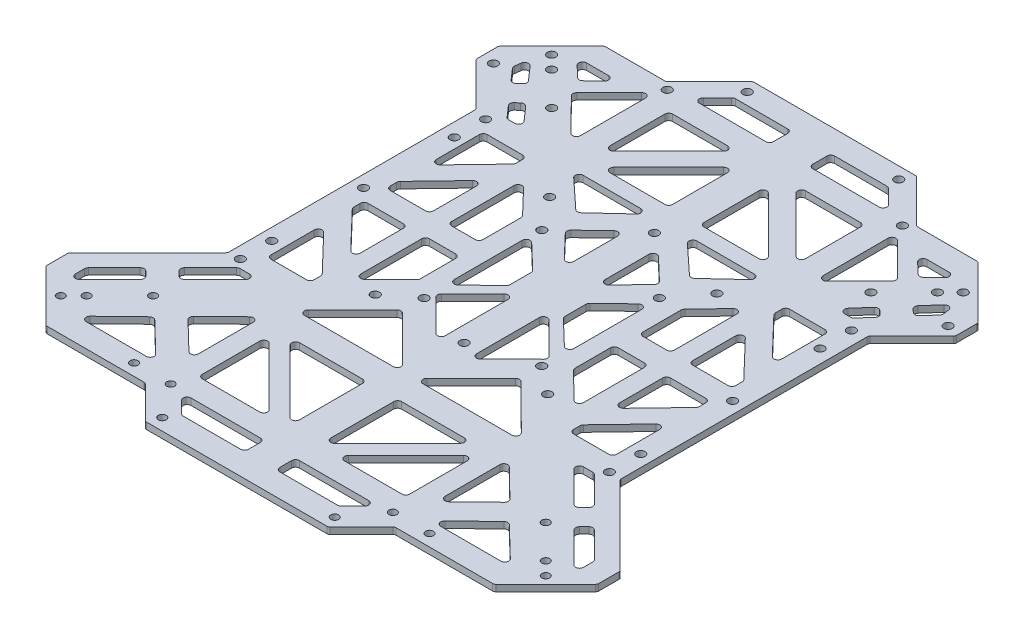
SolidWorks part; units mm, degrees
ref_plane "Ön Düzlem" through (0, 0, 0) normal (0, 0, 1) x (1, 0, 0)
ref_plane "Üst Düzlem" through (0, 0, 0) normal (0, 1, 0) x (1, 0, 0)
ref_plane "Sağ Düzlem" through (0, 0, 0) normal (1, 0, 0) x (0, 0, -1)
sketch "Çizim1" plane through (0, 0, 0) normal (0, 1, 0) x (1, 0, 0)
  line L0 (-126.5115, 0) -> (-22.8808, 0) construction
  line L1 (0, -165.8604) -> (0, 125.495) construction
  line L10 (105.5269, -77.9056) -> (75.1213, -47.5)
  line L11 (105.5269, -86.6056) -> (105.5269, -77.9056)
  line L12 (85.7279, -106.4046) -> (105.5269, -86.6056)
  line L13 (47.7279, -106.4046) -> (85.7279, -106.4046)
  line L14 (35, -119.1325) -> (47.7279, -106.4046)
  line L15 (35, -119.1325) -> (-35, -119.1325)
  line L17 (75.1213, -47.5) -> (75.1213, 0)
  line L19 (6, -104.1325) -> (6, -108.6325)
  line L20 (7.5, -110.1325) -> (29.5, -110.1325)
  line L21 (30.5607, -109.6932) -> (35.0607, -105.1932)
  line L22 (34, -102.6325) -> (7.5, -102.6325)
  line L24 (39.6933, -70.6325) -> (39.6933, -92.6325)
  line L25 (38.1933, -94.1325) -> (16.1933, -94.1325)
  line L26 (15.1326, -91.5718) -> (37.1326, -69.5718)
  line L27 (6, -65.0493) -> (6, -89.1325)
  line L28 (8.5625, -90.1913) -> (32.5625, -66.1081)
  line L29 (31.5, -63.5493) -> (7.5, -63.5493)
  line L30 (66.8113, -83.7022) -> (55.3113, -94.8265)
  line L31 (56.3542, -97.4046) -> (79.3542, -97.4046)
  line L32 (80.3971, -94.8265) -> (68.8971, -83.7022)
  line L36 (49.7362, -87.6977) -> (60.5174, -77.2687)
  line L37 (60.5247, -75.1195) -> (49.7434, -64.5485)
  line L38 (47.1933, -65.6196) -> (47.1933, -86.6196)
  line L39 (21.6344, -34.0457) -> (4.6344, -50.9868)
  line L40 (5.6933, -53.5493) -> (39.6933, -53.5493)
  line L41 (40.7521, -50.9868) -> (23.7521, -34.0457)
  line L42 (6, -9.3078) -> (6, -33.3078)
  line L43 (8.5588, -34.3703) -> (20.6004, -22.3703)
  line L44 (20.6004, -20.2453) -> (8.5588, -8.2453)
  line L45 (10.5, 4) -> (10.5, -4)
  line L46 (10.9615, -5.0824) -> (20.3424, -14.0824)
  line L47 (22.8808, -13) -> (22.8808, 13)
  line L49 (84.7746, -69.1741) -> (83.0069, -70.9419)
  line L50 (83.0069, -73.0632) -> (94.6741, -84.7305)
  line L51 (97.2348, -83.6698) -> (97.2348, -80.1343)
  line L52 (96.7954, -79.0736) -> (86.8959, -69.1741)
  line L53 (87.603, -59.9817) -> (82.3234, -65.2614) construction
  line L54 (63.915, -50.35) -> (67.4505, -50.35)
  line L55 (74.5216, -64.5779) -> (62.8543, -52.9107)
  line L56 (78.4107, -62.8102) -> (76.6429, -64.5779)
  line L57 (68.5112, -50.7893) -> (78.4107, -60.6888)
  line L58 (51.1213, -41.35) -> (64.6213, -41.35)
  line L59 (66.1213, -39.85) -> (66.1213, -23.35)
  line L60 (63.5389, -22.3115) -> (50.0389, -36.3828)
  line L61 (49.6213, -37.4212) -> (49.6213, -39.85)
  line L62 (49.6213, -5.7546) -> (49.6213, -22.2546)
  line L63 (52.2037, -23.293) -> (65.7037, -9.2218)
  line L64 (66.1213, -8.1833) -> (66.1213, -5.7546)
  line L65 (64.6213, -4.2546) -> (51.1213, -4.2546)
  line L66 (29.6213, -5.75) -> (29.6213, -19.25)
  line L67 (30.0715, -20.3214) -> (40.0715, -30.1194)
  line L68 (42.6213, -29.048) -> (42.6213, -5.75)
  line L69 (41.1213, -4.25) -> (31.1213, -4.25)
  line L70 (-105.5269, -86.6056) -> (-105.5269, -77.9056)
  line L71 (-105.5269, -77.9056) -> (-75.1213, -47.5)
  line L72 (-85.7279, -106.4046) -> (-105.5269, -86.6056)
  line L73 (-87.603, -59.9817) -> (-82.3234, -65.2614) construction
  line L74 (-41.1213, -4.25) -> (-31.1213, -4.25)
  line L75 (-42.6213, -29.048) -> (-42.6213, -5.75)
  line L76 (-30.0715, -20.3214) -> (-40.0715, -30.1194)
  line L77 (-29.6213, -5.75) -> (-29.6213, -19.25)
  line L78 (-64.6213, -4.2546) -> (-51.1213, -4.2546)
  line L79 (-66.1213, -8.1833) -> (-66.1213, -5.7546)
  line L80 (-52.2037, -23.293) -> (-65.7037, -9.2218)
  line L81 (-49.6213, -5.7546) -> (-49.6213, -22.2546)
  line L82 (-49.6213, -37.4212) -> (-49.6213, -39.85)
  line L83 (-63.5389, -22.3115) -> (-50.0389, -36.3828)
  line L84 (-66.1213, -39.85) -> (-66.1213, -23.35)
  line L85 (-51.1213, -41.35) -> (-64.6213, -41.35)
  line L86 (-68.5112, -50.7893) -> (-78.4107, -60.6888)
  line L87 (-78.4107, -62.8102) -> (-76.6429, -64.5779)
  line L88 (-74.5216, -64.5779) -> (-62.8543, -52.9107)
  line L89 (-63.915, -50.35) -> (-67.4505, -50.35)
  line L90 (-96.7954, -79.0736) -> (-86.8959, -69.1741)
  line L91 (-97.2348, -83.6698) -> (-97.2348, -80.1343)
  line L92 (-83.0069, -73.0632) -> (-94.6741, -84.7305)
  line L93 (-84.7746, -69.1741) -> (-83.0069, -70.9419)
  line L95 (-22.8808, -13) -> (-22.8808, 0)
  line L96 (-10.9615, -5.0824) -> (-20.3424, -14.0824)
  line L97 (-10.5, 0) -> (-10.5, -4)
  line L98 (-20.6004, -20.2453) -> (-8.5588, -8.2453)
  line L99 (-8.5588, -34.3703) -> (-20.6004, -22.3703)
  line L100 (-6, -9.3078) -> (-6, -33.3078)
  line L101 (-40.7521, -50.9868) -> (-23.7521, -34.0457)
  line L102 (-5.6933, -53.5493) -> (-39.6933, -53.5493)
  line L103 (-21.6344, -34.0457) -> (-4.6344, -50.9868)
  line L104 (-47.1933, -65.6196) -> (-47.1933, -86.6196)
  line L105 (-60.5247, -75.1195) -> (-49.7434, -64.5485)
  line L106 (-49.7362, -87.6977) -> (-60.5174, -77.2687)
  line L107 (-80.3971, -94.8265) -> (-68.8971, -83.7022)
  line L108 (-56.3542, -97.4046) -> (-79.3542, -97.4046)
  line L109 (-66.8113, -83.7022) -> (-55.3113, -94.8265)
  line L110 (-31.5, -63.5493) -> (-7.5, -63.5493)
  line L111 (-8.5625, -90.1913) -> (-32.5625, -66.1081)
  line L112 (-6, -65.0493) -> (-6, -89.1325)
  line L113 (-15.1326, -91.5718) -> (-37.1326, -69.5718)
  line L114 (-38.1933, -94.1325) -> (-16.1933, -94.1325)
  line L115 (-39.6933, -70.6325) -> (-39.6933, -92.6325)
  line L116 (-34, -102.6325) -> (-7.5, -102.6325)
  line L117 (-30.5607, -109.6932) -> (-35.0607, -105.1932)
  line L118 (-7.5, -110.1325) -> (-29.5, -110.1325)
  line L119 (-6, -104.1325) -> (-6, -108.6325)
  line L120 (-75.1213, -47.5) -> (-75.1213, 0)
  line L121 (-35, -119.1325) -> (-47.7279, -106.4046)
  line L122 (-47.7279, -106.4046) -> (-85.7279, -106.4046)
  line L124 (75.1213, 0) -> (75.1213, 47.5)
  line L125 (75.1213, 47.5) -> (91.7383, 64.117)
  line L126 (91.7383, 64.117) -> (91.7383, 72.817)
  line L127 (91.7383, 72.817) -> (71.4444, 93.111)
  line L128 (71.4444, 93.111) -> (47.9444, 93.111)
  line L129 (47.9444, 93.111) -> (31.3274, 109.728)
  line L130 (31.3274, 109.728) -> (-31.3274, 109.728)
  line L131 (63.5389, 22.3115) -> (50.0389, 36.3828)
  line L132 (66.1213, 39.85) -> (66.1213, 23.35)
  line L133 (51.1213, 41.35) -> (64.6213, 41.35)
  line L134 (49.6213, 37.4212) -> (49.6213, 39.85)
  line L135 (66.1213, 8.1833) -> (66.1213, 5.7546)
  line L136 (52.2037, 23.293) -> (65.7037, 9.2218)
  line L137 (49.6213, 5.7546) -> (49.6213, 22.2546)
  line L138 (64.6213, 4.2546) -> (51.1213, 4.2546)
  line L139 (41.1213, 4.2546) -> (32.1213, 4.2546)
  line L140 (30.6213, 5.7546) -> (30.6213, 20.2546)
  line L141 (31.0389, 21.293) -> (40.0389, 30.6739)
  line L142 (42.6213, 29.6354) -> (42.6213, 5.7546)
  line L143 (10.9615, 5.0824) -> (20.3424, 14.0824)
  line L144 (22.8808, 0) -> (141.8188, 0) construction
  line L145 (62.0023, 52.8424) -> (66.6337, 58.0913)
  line L146 (68.7509, 58.2236) -> (70.0256, 57.0989)
  line L147 (70.1579, 54.9817) -> (66.519, 50.8576)
  line L150 (65.3942, 50.35) -> (63.1271, 50.35)
  line L151 (70.1198, 63.017) -> (74.1298, 59.4788) construction
  line L152 (78.0974, 63.9797) -> (81.7363, 68.1038)
  line L153 (74.7055, 64.9722) -> (75.9802, 63.8474)
  line L154 (79.2045, 72.3382) -> (74.5731, 67.0894)
  line L155 (82.0999, 69.283) -> (81.8176, 71.5326)
  line L156 (60.9579, 84.111) -> (69.3579, 84.111)
  line L157 (70.3923, 81.5248) -> (66.1923, 77.5248)
  line L158 (64.1234, 77.5248) -> (59.9234, 81.5248)
  line L159 (6, 32.6354) -> (6, 15.8354)
  line L160 (8.585, 14.7997) -> (16.976, 23.5902)
  line L161 (16.9266, 25.7109) -> (8.5357, 33.7204)
  line L162 (9.7302, 43.598) -> (20.7302, 33.4)
  line L163 (22.7698, 33.4) -> (33.7698, 43.598)
  line L164 (32.75, 46.198) -> (10.75, 46.198)
  line L165 (9, 100.728) -> (29.0094, 100.728)
  line L166 (30.071, 100.2877) -> (35.4616, 94.8877)
  line L167 (34.4, 92.328) -> (9, 92.328)
  line L168 (7.5, 93.828) -> (7.5, 99.228)
  line L169 (6, 74.698) -> (6, 53.698)
  line L170 (7.5, 52.198) -> (28.5, 52.198)
  line L171 (29.5607, 54.7587) -> (8.5607, 75.7587)
  line L172 (16.4335, 73.1892) -> (24.0883, 65.5343) construction
  line L173 (37.4246, 82.1227) -> (37.4246, 61.1227)
  line L174 (14.9246, 83.6227) -> (35.9246, 83.6227)
  line L175 (34.864, 60.062) -> (13.864, 81.062)
  line L176 (46.4246, 83.7244) -> (46.4246, 58.8244)
  line L177 (48.9917, 57.7702) -> (61.3661, 70.2958)
  line L178 (61.3597, 72.4107) -> (48.9853, 84.785)
  line L179 (-10.5, 0) -> (10.5, 0) construction
  line L180 (-22.8808, -13) -> (-22.8808, 13)
  line L181 (-10.5, 4) -> (-10.5, -4)
  line L182 (-75.1213, 0) -> (-75.1213, 47.5)
  line L183 (-16.4335, 73.1892) -> (-24.0883, 65.5343) construction
  line L184 (-61.3597, 72.4107) -> (-48.9853, 84.785)
  line L185 (-48.9917, 57.7702) -> (-61.3661, 70.2958)
  line L186 (-46.4246, 83.7244) -> (-46.4246, 58.8244)
  line L187 (-34.864, 60.062) -> (-13.864, 81.062)
  line L188 (-14.9246, 83.6227) -> (-35.9246, 83.6227)
  line L189 (-37.4246, 82.1227) -> (-37.4246, 61.1227)
  line L190 (-29.5607, 54.7587) -> (-8.5607, 75.7587)
  line L191 (-7.5, 52.198) -> (-28.5, 52.198)
  line L192 (-6, 74.698) -> (-6, 53.698)
  line L193 (-7.5, 93.828) -> (-7.5, 99.228)
  line L194 (-34.4, 92.328) -> (-9, 92.328)
  line L195 (-30.071, 100.2877) -> (-35.4616, 94.8877)
  line L196 (-9, 100.728) -> (-29.0094, 100.728)
  line L197 (-32.75, 46.198) -> (-10.75, 46.198)
  line L198 (-22.7698, 33.4) -> (-33.7698, 43.598)
  line L199 (-9.7302, 43.598) -> (-20.7302, 33.4)
  line L200 (-16.9266, 25.7109) -> (-8.5357, 33.7204)
  line L201 (-8.585, 14.7997) -> (-16.976, 23.5902)
  line L202 (-6, 32.6354) -> (-6, 15.8354)
  line L203 (-64.1234, 77.5248) -> (-59.9234, 81.5248)
  line L204 (-70.3923, 81.5248) -> (-66.1923, 77.5248)
  line L205 (-60.9579, 84.111) -> (-69.3579, 84.111)
  line L206 (-82.0999, 69.283) -> (-81.8176, 71.5326)
  line L207 (-79.2045, 72.3382) -> (-74.5731, 67.0894)
  line L208 (-74.7055, 64.9722) -> (-75.9802, 63.8474)
  line L209 (-78.0974, 63.9797) -> (-81.7363, 68.1038)
  line L210 (-10.9615, 5.0824) -> (-20.3424, 14.0824)
  line L211 (-42.6213, 29.6354) -> (-42.6213, 5.7546)
  line L212 (-31.0389, 21.293) -> (-40.0389, 30.6739)
  line L213 (-30.6213, 5.7546) -> (-30.6213, 20.2546)
  line L214 (-41.1213, 4.2546) -> (-32.1213, 4.2546)
  line L215 (-64.6213, 4.2546) -> (-51.1213, 4.2546)
  line L216 (-49.6213, 5.7546) -> (-49.6213, 22.2546)
  line L217 (-52.2037, 23.293) -> (-65.7037, 9.2218)
  line L218 (-66.1213, 8.1833) -> (-66.1213, 5.7546)
  line L219 (-49.6213, 37.4212) -> (-49.6213, 39.85)
  line L220 (-51.1213, 41.35) -> (-64.6213, 41.35)
  line L221 (-66.1213, 39.85) -> (-66.1213, 23.35)
  line L222 (-63.5389, 22.3115) -> (-50.0389, 36.3828)
  line L223 (-47.9444, 93.111) -> (-31.3274, 109.728)
  line L224 (-71.4444, 93.111) -> (-47.9444, 93.111)
  line L225 (-91.7383, 72.817) -> (-71.4444, 93.111)
  line L226 (-91.7383, 64.117) -> (-91.7383, 72.817)
  line L227 (-75.1213, 47.5) -> (-91.7383, 64.117)
  line L228 (-70.1579, 54.9817) -> (-66.519, 50.8576)
  line L229 (-68.7509, 58.2236) -> (-70.0256, 57.0989)
  line L230 (-62.0023, 52.8424) -> (-66.6337, 58.0913)
  line L231 (-65.3942, 50.35) -> (-63.1271, 50.35)
  arc A0 (29.5, -110.1325) -> (30.5607, -109.6932) centre (29.5, -108.6325) ccw
  arc A1 (35.0607, -105.1932) -> (34, -102.6325) centre (34, -104.1325) ccw
  arc A2 (6, -104.1325) -> (7.5, -102.6325) centre (7.5, -104.1325) cw
  arc A3 (6, -108.6325) -> (7.5, -110.1325) centre (7.5, -108.6325) ccw
  arc A4 (39.6933, -70.6325) -> (37.1326, -69.5718) centre (38.1933, -70.6325) ccw
  arc A5 (39.6933, -92.6325) -> (38.1933, -94.1325) centre (38.1933, -92.6325) cw
  arc A6 (16.1933, -94.1325) -> (15.1326, -91.5718) centre (16.1933, -92.6325) cw
  arc A7 (6, -89.1325) -> (8.5625, -90.1913) centre (7.5, -89.1325) ccw
  arc A8 (32.5625, -66.1081) -> (31.5, -63.5493) centre (31.5, -65.0493) ccw
  arc A9 (6, -65.0493) -> (7.5, -63.5493) centre (7.5, -65.0493) cw
  arc A10 (79.3542, -97.4046) -> (80.3971, -94.8265) centre (79.3542, -95.9046) ccw
  arc A11 (55.3113, -94.8265) -> (56.3542, -97.4046) centre (56.3542, -95.9046) ccw
  arc A12 (66.8113, -83.7022) -> (68.8971, -83.7022) centre (67.8542, -84.7803) cw
  arc A16 (60.5174, -77.2687) -> (60.5247, -75.1195) centre (59.4745, -76.1905) ccw
  arc A17 (49.7434, -64.5485) -> (47.1933, -65.6196) centre (48.6933, -65.6196) ccw
  arc A18 (49.7362, -87.6977) -> (47.1933, -86.6196) centre (48.6933, -86.6196) cw
  arc A19 (39.6933, -53.5493) -> (40.7521, -50.9868) centre (39.6933, -52.0493) ccw
  arc A20 (4.6344, -50.9868) -> (5.6933, -53.5493) centre (5.6933, -52.0493) ccw
  arc A21 (21.6344, -34.0457) -> (23.7521, -34.0457) centre (22.6933, -35.1082) cw
  arc A22 (6, -9.3078) -> (8.5588, -8.2453) centre (7.5, -9.3078) cw
  arc A23 (20.6004, -22.3703) -> (20.6004, -20.2453) centre (19.5416, -21.3078) ccw
  arc A24 (6, -33.3078) -> (8.5588, -34.3703) centre (7.5, -33.3078) ccw
  arc A25 (20.3424, -14.0824) -> (22.8808, -13) centre (21.3808, -13) ccw
  arc A26 (10.5, -4) -> (10.9615, -5.0824) centre (12, -4) ccw
  arc A27 (83.0069, -70.9419) -> (83.0069, -73.0632) centre (84.0675, -72.0025) ccw
  arc A28 (84.7746, -69.1741) -> (86.8959, -69.1741) centre (85.8353, -70.2348) cw
  arc A29 (97.2348, -80.1343) -> (96.7954, -79.0736) centre (95.7348, -80.1343) ccw
  arc A30 (94.6741, -84.7305) -> (97.2348, -83.6698) centre (95.7348, -83.6698) ccw
  arc A31 (62.8543, -52.9107) -> (63.915, -50.35) centre (63.915, -51.85) cw
  arc A32 (76.6429, -64.5779) -> (74.5216, -64.5779) centre (75.5822, -63.5173) cw
  arc A33 (78.4107, -62.8102) -> (78.4107, -60.6888) centre (77.35, -61.7495) ccw
  arc A34 (67.4505, -50.35) -> (68.5112, -50.7893) centre (67.4505, -51.85) cw
  arc A35 (66.1213, -23.35) -> (63.5389, -22.3115) centre (64.6213, -23.35) ccw
  arc A36 (64.6213, -41.35) -> (66.1213, -39.85) centre (64.6213, -39.85) ccw
  arc A37 (51.1213, -41.35) -> (49.6213, -39.85) centre (51.1213, -39.85) cw
  arc A38 (50.0389, -36.3828) -> (49.6213, -37.4212) centre (51.1213, -37.4212) ccw
  arc A39 (66.1213, -5.7546) -> (64.6213, -4.2546) centre (64.6213, -5.7546) ccw
  arc A40 (65.7037, -9.2218) -> (66.1213, -8.1833) centre (64.6213, -8.1833) ccw
  arc A41 (49.6213, -22.2546) -> (52.2037, -23.293) centre (51.1213, -22.2546) ccw
  arc A42 (49.6213, -5.7546) -> (51.1213, -4.2546) centre (51.1213, -5.7546) cw
  arc A43 (29.6213, -5.75) -> (31.1213, -4.25) centre (31.1213, -5.75) cw
  arc A44 (42.6213, -5.75) -> (41.1213, -4.25) centre (41.1213, -5.75) ccw
  arc A45 (40.0715, -30.1194) -> (42.6213, -29.048) centre (41.1213, -29.048) ccw
  arc A46 (29.6213, -19.25) -> (30.0715, -20.3214) centre (31.1213, -19.25) ccw
  arc A47 (-29.6213, -19.25) -> (-30.0715, -20.3214) centre (-31.1213, -19.25) cw
  arc A48 (-40.0715, -30.1194) -> (-42.6213, -29.048) centre (-41.1213, -29.048) cw
  arc A49 (-42.6213, -5.75) -> (-41.1213, -4.25) centre (-41.1213, -5.75) cw
  arc A50 (-29.6213, -5.75) -> (-31.1213, -4.25) centre (-31.1213, -5.75) ccw
  arc A51 (-49.6213, -5.7546) -> (-51.1213, -4.2546) centre (-51.1213, -5.7546) ccw
  arc A52 (-49.6213, -22.2546) -> (-52.2037, -23.293) centre (-51.1213, -22.2546) cw
  arc A53 (-65.7037, -9.2218) -> (-66.1213, -8.1833) centre (-64.6213, -8.1833) cw
  arc A54 (-66.1213, -5.7546) -> (-64.6213, -4.2546) centre (-64.6213, -5.7546) cw
  arc A55 (-50.0389, -36.3828) -> (-49.6213, -37.4212) centre (-51.1213, -37.4212) cw
  arc A56 (-51.1213, -41.35) -> (-49.6213, -39.85) centre (-51.1213, -39.85) ccw
  arc A57 (-64.6213, -41.35) -> (-66.1213, -39.85) centre (-64.6213, -39.85) cw
  arc A58 (-66.1213, -23.35) -> (-63.5389, -22.3115) centre (-64.6213, -23.35) cw
  arc A59 (-67.4505, -50.35) -> (-68.5112, -50.7893) centre (-67.4505, -51.85) ccw
  arc A60 (-78.4107, -62.8102) -> (-78.4107, -60.6888) centre (-77.35, -61.7495) cw
  arc A61 (-76.6429, -64.5779) -> (-74.5216, -64.5779) centre (-75.5822, -63.5173) ccw
  arc A62 (-62.8543, -52.9107) -> (-63.915, -50.35) centre (-63.915, -51.85) ccw
  arc A63 (-94.6741, -84.7305) -> (-97.2348, -83.6698) centre (-95.7348, -83.6698) cw
  arc A64 (-97.2348, -80.1343) -> (-96.7954, -79.0736) centre (-95.7348, -80.1343) cw
  arc A65 (-84.7746, -69.1741) -> (-86.8959, -69.1741) centre (-85.8353, -70.2348) ccw
  arc A66 (-83.0069, -70.9419) -> (-83.0069, -73.0632) centre (-84.0675, -72.0025) cw
  arc A67 (-10.5, -4) -> (-10.9615, -5.0824) centre (-12, -4) cw
  arc A68 (-20.3424, -14.0824) -> (-22.8808, -13) centre (-21.3808, -13) cw
  arc A69 (-6, -33.3078) -> (-8.5588, -34.3703) centre (-7.5, -33.3078) cw
  arc A70 (-20.6004, -22.3703) -> (-20.6004, -20.2453) centre (-19.5416, -21.3078) cw
  arc A71 (-6, -9.3078) -> (-8.5588, -8.2453) centre (-7.5, -9.3078) ccw
  arc A72 (-21.6344, -34.0457) -> (-23.7521, -34.0457) centre (-22.6933, -35.1082) ccw
  arc A73 (-4.6344, -50.9868) -> (-5.6933, -53.5493) centre (-5.6933, -52.0493) cw
  arc A74 (-39.6933, -53.5493) -> (-40.7521, -50.9868) centre (-39.6933, -52.0493) cw
  arc A75 (-49.7362, -87.6977) -> (-47.1933, -86.6196) centre (-48.6933, -86.6196) ccw
  arc A76 (-49.7434, -64.5485) -> (-47.1933, -65.6196) centre (-48.6933, -65.6196) cw
  arc A77 (-60.5174, -77.2687) -> (-60.5247, -75.1195) centre (-59.4745, -76.1905) cw
  arc A78 (-66.8113, -83.7022) -> (-68.8971, -83.7022) centre (-67.8542, -84.7803) ccw
  arc A79 (-55.3113, -94.8265) -> (-56.3542, -97.4046) centre (-56.3542, -95.9046) cw
  arc A80 (-79.3542, -97.4046) -> (-80.3971, -94.8265) centre (-79.3542, -95.9046) cw
  arc A81 (-6, -65.0493) -> (-7.5, -63.5493) centre (-7.5, -65.0493) ccw
  arc A82 (-32.5625, -66.1081) -> (-31.5, -63.5493) centre (-31.5, -65.0493) cw
  arc A83 (-6, -89.1325) -> (-8.5625, -90.1913) centre (-7.5, -89.1325) cw
  arc A84 (-16.1933, -94.1325) -> (-15.1326, -91.5718) centre (-16.1933, -92.6325) ccw
  arc A85 (-39.6933, -92.6325) -> (-38.1933, -94.1325) centre (-38.1933, -92.6325) ccw
  arc A86 (-39.6933, -70.6325) -> (-37.1326, -69.5718) centre (-38.1933, -70.6325) cw
  arc A87 (-6, -108.6325) -> (-7.5, -110.1325) centre (-7.5, -108.6325) cw
  arc A88 (-6, -104.1325) -> (-7.5, -102.6325) centre (-7.5, -104.1325) ccw
  arc A89 (-35.0607, -105.1932) -> (-34, -102.6325) centre (-34, -104.1325) cw
  arc A90 (-29.5, -110.1325) -> (-30.5607, -109.6932) centre (-29.5, -108.6325) cw
  arc A91 (66.1213, 23.35) -> (63.5389, 22.3115) centre (64.6213, 23.35) cw
  arc A92 (64.6213, 41.35) -> (66.1213, 39.85) centre (64.6213, 39.85) cw
  arc A93 (51.1213, 41.35) -> (49.6213, 39.85) centre (51.1213, 39.85) ccw
  arc A94 (50.0389, 36.3828) -> (49.6213, 37.4212) centre (51.1213, 37.4212) cw
  arc A95 (65.7037, 9.2218) -> (66.1213, 8.1833) centre (64.6213, 8.1833) cw
  arc A96 (49.6213, 22.2546) -> (52.2037, 23.293) centre (51.1213, 22.2546) cw
  arc A97 (66.1213, 5.7546) -> (64.6213, 4.2546) centre (64.6213, 5.7546) cw
  arc A98 (49.6213, 5.7546) -> (51.1213, 4.2546) centre (51.1213, 5.7546) ccw
  arc A99 (32.1213, 4.2546) -> (30.6213, 5.7546) centre (32.1213, 5.7546) cw
  arc A100 (41.1213, 4.2546) -> (42.6213, 5.7546) centre (41.1213, 5.7546) ccw
  arc A101 (40.0389, 30.6739) -> (42.6213, 29.6354) centre (41.1213, 29.6354) cw
  arc A102 (30.6213, 20.2546) -> (31.0389, 21.293) centre (32.1213, 20.2546) cw
  arc A103 (10.5, 4) -> (10.9615, 5.0824) centre (12, 4) cw
  arc A104 (20.3424, 14.0824) -> (22.8808, 13) centre (21.3808, 13) cw
  arc A105 (66.6337, 58.0913) -> (68.7509, 58.2236) centre (67.7584, 57.0989) cw
  arc A106 (70.0256, 57.0989) -> (70.1579, 54.9817) centre (69.0332, 55.9741) cw
  arc A107 (66.519, 50.8576) -> (65.3942, 50.35) centre (65.3942, 51.85) cw
  arc A108 (62.0023, 52.8424) -> (63.1271, 50.35) centre (63.1271, 51.85) ccw
  arc A109 (75.9802, 63.8474) -> (78.0974, 63.9797) centre (76.9726, 64.9722) ccw
  arc A110 (74.5731, 67.0894) -> (74.7055, 64.9722) centre (75.6979, 66.0969) ccw
  arc A111 (81.7363, 68.1038) -> (82.0999, 69.283) centre (80.6115, 69.0963) ccw
  arc A112 (79.2045, 72.3382) -> (81.8176, 71.5326) centre (80.3292, 71.3458) cw
  arc A113 (69.3579, 84.111) -> (70.3923, 81.5248) centre (69.3579, 82.611) cw
  arc A114 (66.1923, 77.5248) -> (64.1234, 77.5248) centre (65.1579, 78.611) cw
  arc A115 (60.9579, 84.111) -> (59.9234, 81.5248) centre (60.9579, 82.611) ccw
  arc A116 (16.976, 23.5902) -> (16.9266, 25.7109) centre (15.8909, 24.6259) ccw
  arc A117 (6, 15.8354) -> (8.585, 14.7997) centre (7.5, 15.8354) ccw
  arc A118 (6, 32.6354) -> (8.5357, 33.7204) centre (7.5, 32.6354) cw
  arc A119 (33.7698, 43.598) -> (32.75, 46.198) centre (32.75, 44.698) ccw
  arc A120 (20.7302, 33.4) -> (22.7698, 33.4) centre (21.75, 34.5) ccw
  arc A121 (9.7302, 43.598) -> (10.75, 46.198) centre (10.75, 44.698) cw
  arc A122 (35.4616, 94.8877) -> (34.4, 92.328) centre (34.4, 93.828) cw
  arc A123 (29.0094, 100.728) -> (30.071, 100.2877) centre (29.0094, 99.228) cw
  arc A124 (9, 100.728) -> (7.5, 99.228) centre (9, 99.228) ccw
  arc A125 (9, 92.328) -> (7.5, 93.828) centre (9, 93.828) cw
  arc A126 (28.5, 52.198) -> (29.5607, 54.7587) centre (28.5, 53.698) ccw
  arc A127 (6, 53.698) -> (7.5, 52.198) centre (7.5, 53.698) ccw
  arc A128 (6, 74.698) -> (8.5607, 75.7587) centre (7.5, 74.698) cw
  arc A129 (35.9246, 83.6227) -> (37.4246, 82.1227) centre (35.9246, 82.1227) cw
  arc A130 (37.4246, 61.1227) -> (34.864, 60.062) centre (35.9246, 61.1227) cw
  arc A131 (14.9246, 83.6227) -> (13.864, 81.062) centre (14.9246, 82.1227) ccw
  arc A132 (46.4246, 83.7244) -> (48.9853, 84.785) centre (47.9246, 83.7244) cw
  arc A133 (46.4246, 58.8244) -> (48.9917, 57.7702) centre (47.9246, 58.8244) ccw
  arc A134 (61.3661, 70.2958) -> (61.3597, 72.4107) centre (60.299, 71.35) ccw
  arc A135 (-61.3661, 70.2958) -> (-61.3597, 72.4107) centre (-60.299, 71.35) cw
  arc A136 (-46.4246, 58.8244) -> (-48.9917, 57.7702) centre (-47.9246, 58.8244) cw
  arc A137 (-46.4246, 83.7244) -> (-48.9853, 84.785) centre (-47.9246, 83.7244) ccw
  arc A138 (-14.9246, 83.6227) -> (-13.864, 81.062) centre (-14.9246, 82.1227) cw
  arc A139 (-37.4246, 61.1227) -> (-34.864, 60.062) centre (-35.9246, 61.1227) ccw
  arc A140 (-35.9246, 83.6227) -> (-37.4246, 82.1227) centre (-35.9246, 82.1227) ccw
  arc A141 (-6, 74.698) -> (-8.5607, 75.7587) centre (-7.5, 74.698) ccw
  arc A142 (-6, 53.698) -> (-7.5, 52.198) centre (-7.5, 53.698) cw
  arc A143 (-28.5, 52.198) -> (-29.5607, 54.7587) centre (-28.5, 53.698) cw
  arc A144 (-9, 92.328) -> (-7.5, 93.828) centre (-9, 93.828) ccw
  arc A145 (-9, 100.728) -> (-7.5, 99.228) centre (-9, 99.228) cw
  arc A146 (-29.0094, 100.728) -> (-30.071, 100.2877) centre (-29.0094, 99.228) ccw
  arc A147 (-35.4616, 94.8877) -> (-34.4, 92.328) centre (-34.4, 93.828) ccw
  arc A148 (-9.7302, 43.598) -> (-10.75, 46.198) centre (-10.75, 44.698) ccw
  arc A149 (-20.7302, 33.4) -> (-22.7698, 33.4) centre (-21.75, 34.5) cw
  arc A150 (-33.7698, 43.598) -> (-32.75, 46.198) centre (-32.75, 44.698) cw
  arc A151 (-6, 32.6354) -> (-8.5357, 33.7204) centre (-7.5, 32.6354) ccw
  arc A152 (-6, 15.8354) -> (-8.585, 14.7997) centre (-7.5, 15.8354) cw
  arc A153 (-16.976, 23.5902) -> (-16.9266, 25.7109) centre (-15.8909, 24.6259) cw
  arc A154 (-60.9579, 84.111) -> (-59.9234, 81.5248) centre (-60.9579, 82.611) cw
  arc A155 (-66.1923, 77.5248) -> (-64.1234, 77.5248) centre (-65.1579, 78.611) ccw
  arc A156 (-69.3579, 84.111) -> (-70.3923, 81.5248) centre (-69.3579, 82.611) ccw
  arc A157 (-79.2045, 72.3382) -> (-81.8176, 71.5326) centre (-80.3292, 71.3458) ccw
  arc A158 (-81.7363, 68.1038) -> (-82.0999, 69.283) centre (-80.6115, 69.0963) cw
  arc A159 (-74.5731, 67.0894) -> (-74.7055, 64.9722) centre (-75.6979, 66.0969) cw
  arc A160 (-75.9802, 63.8474) -> (-78.0974, 63.9797) centre (-76.9726, 64.9722) cw
  arc A161 (-20.3424, 14.0824) -> (-22.8808, 13) centre (-21.3808, 13) ccw
  arc A162 (-10.5, 4) -> (-10.9615, 5.0824) centre (-12, 4) ccw
  arc A163 (-30.6213, 20.2546) -> (-31.0389, 21.293) centre (-32.1213, 20.2546) ccw
  arc A164 (-40.0389, 30.6739) -> (-42.6213, 29.6354) centre (-41.1213, 29.6354) ccw
  arc A165 (-41.1213, 4.2546) -> (-42.6213, 5.7546) centre (-41.1213, 5.7546) cw
  arc A166 (-32.1213, 4.2546) -> (-30.6213, 5.7546) centre (-32.1213, 5.7546) ccw
  arc A167 (-49.6213, 5.7546) -> (-51.1213, 4.2546) centre (-51.1213, 5.7546) cw
  arc A168 (-66.1213, 5.7546) -> (-64.6213, 4.2546) centre (-64.6213, 5.7546) ccw
  arc A169 (-49.6213, 22.2546) -> (-52.2037, 23.293) centre (-51.1213, 22.2546) ccw
  arc A170 (-65.7037, 9.2218) -> (-66.1213, 8.1833) centre (-64.6213, 8.1833) ccw
  arc A171 (-50.0389, 36.3828) -> (-49.6213, 37.4212) centre (-51.1213, 37.4212) ccw
  arc A172 (-51.1213, 41.35) -> (-49.6213, 39.85) centre (-51.1213, 39.85) cw
  arc A173 (-64.6213, 41.35) -> (-66.1213, 39.85) centre (-64.6213, 39.85) ccw
  arc A174 (-66.1213, 23.35) -> (-63.5389, 22.3115) centre (-64.6213, 23.35) ccw
  arc A175 (-70.0256, 57.0989) -> (-70.1579, 54.9817) centre (-69.0332, 55.9741) ccw
  arc A176 (-66.6337, 58.0913) -> (-68.7509, 58.2236) centre (-67.7584, 57.0989) ccw
  arc A177 (-66.519, 50.8576) -> (-65.3942, 50.35) centre (-65.3942, 51.85) ccw
  arc A178 (-62.0023, 52.8424) -> (-63.1271, 50.35) centre (-63.1271, 51.85) cw
  point P14 (75.1213, 0)
  point P24 (0, -119.1325)
  point P29 (-95, 0)
  point P33 (0, 119.1325)
  point P105 (83.8907, -70.058)
  point P152 (42.6213, -32.6177)
  point P155 (29.6213, -19.8803)
  point P298 (0, -119.1325)
  point P299 (-29.6213, -19.8803)
  point P300 (-42.6213, -32.6177)
  point P301 (-75.1213, 0)
  point P357 (67.6261, 59.2161)
  point P360 (71.1503, 56.1064)
  point P363 (66.0711, 50.35)
  point P366 (59.8031, 50.35)
  point P367 (69.3882, 57.6612)
  point P368 (64.2607, 50.35)
  point P577 (0, 109.728)
  dimension "D18" = 1.5
  dimension "D15" = 28
  dimension "D19" = 1.5
  dimension "D24" = 1.5
  dimension "D29" = 1.5
  dimension "D35" = 1.5
  dimension "D39" = 1.5
  dimension "D28" = 1.5
  dimension "D51" = 1.5
  dimension "D55" = 1.5
  dimension "D62" = 1.5
  dimension "D68" = 1.5
  dimension "D75" = 1.5
  dimension "D89" = 1.5
  dimension "D97" = 1.5
  dimension "D102" = 1.5
  dimension "D106" = 1.5
  dimension "D111" = 1.5
  dimension "D112" = 15
  dimension "D113" = 15
  dimension "D115" = 10.75
  dimension "D117" = 1.5
  dimension "D118" = 1.5
  dimension "D119" = 1.5
  dimension "D120" = 1.5
  dimension "D126" = 1.5
  dimension "D127" = 1.5
  dimension "D128" = 1.5
  dimension "D134" = 1.5
  dimension "D135" = 1.5
  dimension "D136" = 1.5
  dimension "D1" = 47.5
  dimension "D2" = 18
  dimension "D3" = 43
  dimension "D4" = 8.7
  dimension "D5" = 28
  dimension "D6" = 38
  dimension "D7" = 35
  dimension "D8" = 135
  dimension "D9" = 225
  dimension "D10" = 135
  dimension "D11" = 135
  dimension "D12" = 135
  dimension "D13" = 7.5
  dimension "D14" = 9
  dimension "D16" = 6
  dimension "D17" = 135
  dimension "D20" = 22
  dimension "D21" = 7.5
  dimension "D22" = 25
  dimension "D23" = 22
  dimension "D25" = 24
  dimension "D26" = 15
  dimension "D27" = 34
  dimension "D30" = 16
  dimension "D31" = 16
  dimension "D32" = 23
  dimension "D33" = 9
  dimension "D34" = 30
  dimension "D36" = 21
  dimension "D37" = 15
  dimension "D38" = 9
  dimension "D40" = 30
  dimension "D41" = 10
  dimension "D42" = 24
  dimension "D43" = 24
  dimension "D44" = 34
  dimension "D45" = 6
  dimension "D46" = 24
  dimension "D47" = 17
  dimension "D48" = 17
  dimension "D49" = 9
  dimension "D50" = 13
  dimension "D52" = 13
  dimension "D53" = 10.5
  dimension "D54" = 4
  dimension "D56" = 7
  dimension "D57" = 5.5
  dimension "D58" = 16.5
  dimension "D59" = 14
  dimension "D60" = 9
  dimension "D61" = 4.5
  dimension "D63" = 13.5
  dimension "D64" = 19.5
  dimension "D65" = 16.5
  dimension "D66" = 9
  dimension "D67" = 9
  dimension "D69" = 19.5
  dimension "D70" = 16.5
  dimension "D71" = 13.5
  dimension "D72" = 9
  dimension "D73" = 7.5
  dimension "D74" = 14
  dimension "D76" = 13.5
  dimension "D77" = 10
  dimension "D78" = 7
  dimension "D79" = 4.25
  dimension "D80" = 47.5
  dimension "D81" = 23.5
  dimension "D82" = 8.7
  dimension "D83" = 28.7
  dimension "D84" = 23.5
  dimension "D85" = 23.5
  dimension "D86" = 135
  dimension "D87" = 135
  dimension "D88" = 7
  dimension "D90" = 12
  dimension "D91" = 13
  dimension "D92" = 14.5
  dimension "D93" = 135
  dimension "D94" = 135
  dimension "D95" = 7
  dimension "D96" = 5.5
  dimension "D98" = 4.7
  dimension "D99" = 9
  dimension "D100" = 8.8
  dimension "D101" = 4.5
  dimension "D103" = 5.8
  dimension "D104" = 9
  dimension "D105" = 8.9
  dimension "D107" = 11.6
  dimension "D108" = 16.8
  dimension "D109" = 6
  dimension "D110" = 9
  dimension "D114" = 22
  dimension "D116" = 21.5
  dimension "D121" = 9
  dimension "D122" = 7.5
  dimension "D123" = 25.4
  dimension "D124" = 7.6301
  dimension "D125" = 8.4
  dimension "D129" = 6
  dimension "D130" = 21
  dimension "D131" = 21
  dimension "D132" = 6
  dimension "D133" = 3.75
  dimension "D137" = 24.9
  dimension "D138" = 5.5
  dimension "D139" = 9
  dimension "D140" = 30
  dimension "D141" = 17.5
extrude "Yükseklik-Ekstrüzyon2" add sketch "Çizim1" along normal blind 2.5 contours L227 L182 L120 L71 L70 L72 L122 L121 L15 L14 L13 L12 L11 L10 L17 L124 L125 L126 L127 L128 L129 L130 L223 L224 L225 L226 A174 L221 A173 L220 A172 L219 A171 L222 A170 L217 A169 L216 A167 L215 A168 L218 A166 L214 A165 L211 A164 L212 region at (0, 0, 8.6044)
sketch "Çizim2" plane through (0, 2.5, 0) normal (0, 1, 0) x (1, 0, 0)
  line L0 (0, 120.2897) -> (0, -148.7666) construction
  line L1 (31.3274, 109.728) -> (-31.3274, 109.728) construction
  line L2 (-177.1004, 0) -> (155.3034, 0) construction
  line L3 (-71.4444, 93.111) -> (-47.9444, 93.111) construction
  line L4 (-75.1213, -47.5) -> (-75.1213, 47.5) construction
  line L5 (35, -119.1325) -> (-35, -119.1325) construction
  line L6 (-47.7279, -106.4046) -> (-85.7279, -106.4046) construction
  line L7 (-105.5269, -86.6056) -> (-105.5269, -77.9056) construction
  line L8 (-73.8202, 75.1929) -> (-89.3625, 90.7351) construction
  line L9 (-75.1213, 47.5) -> (-91.7383, 64.117) construction
  line L10 (-91.7383, 72.817) -> (-71.4444, 93.111) construction
  line L11 (-73.8202, 75.1929) -> (-61.0923, 62.465) construction
  line L12 (-97.9291, -98.8067) -> (-65.4602, -66.3379) construction
  line L13 (-85.7279, -106.4046) -> (-105.5269, -86.6056) construction
  circle A0 centre (-29, 105.228) radius 1.65
  circle A1 centre (-45, 90.611) radius 1.65
  circle A2 centre (0, 40.728) radius 1.65
  circle A3 centre (-73.8202, 75.1929) radius 1.65
  circle A4 centre (-61.0923, 62.465) radius 1.65
  circle A5 centre (-87, 66.111) radius 1.65
  circle A6 centre (-70, 46.111) radius 1.65
  circle A7 centre (-70, 34.111) radius 1.65
  circle A8 centre (-22.5, 20.111) radius 1.65
  circle A9 centre (-70.6213, 0) radius 1.65
  circle A10 centre (22.5, 20.111) radius 1.65
  circle A11 centre (70, 34.111) radius 1.65
  circle A12 centre (70, 46.111) radius 1.65
  circle A13 centre (87, 66.111) radius 1.65
  circle A14 centre (61.0923, 62.465) radius 1.65
  circle A15 centre (73.8202, 75.1929) radius 1.65
  circle A16 centre (45, 90.611) radius 1.65
  circle A17 centre (29, 105.228) radius 1.65
  circle A18 centre (70.6213, 0) radius 1.65
  circle A19 centre (-32, 32.611) radius 1.65
  circle A20 centre (32, 32.611) radius 1.65
  circle A21 centre (-33, -114.6325) radius 1.5
  circle A22 centre (-22.5, -24.9325) radius 1.65
  circle A23 centre (-70.6213, -35.1325) radius 1.65
  circle A24 centre (0, -32.1325) radius 1.65
  circle A27 centre (-87.8563, -88.734) radius 1.5
  circle A28 centre (-56.5269, -101.9046) radius 1.5
  circle A29 centre (-42.5269, -101.9046) radius 1.5
  circle A30 centre (-70.6213, -47.1325) radius 1.65
  circle A31 centre (70.6213, -47.1325) radius 1.65
  circle A32 centre (42.5269, -101.9046) radius 1.5
  circle A33 centre (56.5269, -101.9046) radius 1.5
  circle A34 centre (87.8563, -88.734) radius 1.5
  circle A36 centre (70.6213, -35.1325) radius 1.65
  circle A37 centre (22.5, -24.9325) radius 1.65
  circle A38 centre (33, -114.6325) radius 1.5
  circle A39 centre (-33, -33.1325) radius 1.65
  circle A40 centre (33, -33.1325) radius 1.65
  circle A41 centre (-92.799, -93.6767) radius 1.5
  circle A42 centre (92.799, -93.6767) radius 1.5
  circle A43 centre (-78.7629, 80.1356) radius 1.65
  circle A44 centre (78.7629, 80.1356) radius 1.65
  point P5 (-29, 105.228)
  point P10 (-45, 90.611)
  point P11 (-73.8202, 75.1929)
  point P12 (-61.0923, 62.465)
  point P13 (-87, 66.111)
  point P14 (-70, 46.111)
  point P15 (-32, 32.611)
  point P16 (-70.6213, 0)
  point P17 (-22.5, 20.111)
  point P18 (0, 40.728)
  point P23 (-70, 34.111)
  point P64 (-22.5, -24.9325)
  point P65 (-33, -33.1325)
  point P66 (-70.6213, -35.1325)
  point P67 (-70.6213, -47.1325)
  point P68 (0, -32.1325)
  point P69 (0, -60.1325)
  point P70 (-87.8563, -88.734)
  point P71 (-74.4213, -75.299)
  point P72 (-56.5269, -101.9046)
  point P73 (-42.5269, -101.9046)
  point P74 (-33, -114.6325)
  point P122 (-81.5913, 82.964)
  point P128 (-95.6274, -96.5051)
  dimension "D3" = 3.3
  dimension "D5" = 45
  dimension "D27" = 3
  dimension "D35" = 4
  dimension "D36" = 4
  dimension "D1" = 29
  dimension "D2" = 4.5
  dimension "D4" = 2.5
  dimension "D6" = 10.99
  dimension "D7" = 18
  dimension "D8" = 87
  dimension "D9" = 27
  dimension "D10" = 19
  dimension "D11" = 10.99
  dimension "D12" = 69
  dimension "D13" = 70
  dimension "D14" = 47
  dimension "D15" = 59
  dimension "D16" = 32
  dimension "D17" = 60.5
  dimension "D18" = 22.5
  dimension "D19" = 73
  dimension "D20" = 4.5
  dimension "D21" = 33
  dimension "D22" = 4.5
  dimension "D23" = 4.5
  dimension "D24" = 14
  dimension "D25" = 63
  dimension "D26" = 59
  dimension "D28" = 22.5
  dimension "D29" = 94.2
  dimension "D30" = 86
  dimension "D31" = 33
  dimension "D32" = 12
  dimension "D33" = 4.5
  dimension "D34" = 72
extrude "Kes-Ekstrüzyon1" cut sketch "Çizim2" along direction (0, 1, 0) on the side against the normal through all contours A41 | A42 | A9 | A8 | A10 | A7 | A6 | A4 | A5 | A1 | A3 | A0 | A17 | A16 | A2 | A11 | A12 | A14 | A13 | A15 | A18 | A20 | A19 | A32 | A33 | A34 | A31 | A36 | A37 | A24 | A22 | A23 | A30 | A38 | A21 | A29 | A28 | A27 | A39 | A40 | A43 | A44 region at (-92.799, 2.5, 93.6767) region at (92.799, 2.5, 93.6767)
fillet "Radyus1" radius 1.17 24 edges at (-91.7383, 1.25, -64.117) (-91.7383, 1.25, -72.817) (-71.4444, 1.25, -93.111) (-47.9444, 1.25, -93.111) (-31.3274, 1.25, -109.728) (31.3274, 1.25, -109.728) (47.9444, 1.25, -93.111) (71.4444, 1.25, -93.111) (91.7383, 1.25, -72.817) (91.7383, 1.25, -64.117) (75.1213, 1.25, -47.5) (75.1213, 1.25, 47.5) (105.5269, 1.25, 77.9056) (105.5269, 1.25, 86.6056) (85.7279, 1.25, 106.4046) (35, 1.25, 119.1325) (-35, 1.25, 119.1325) (-47.7279, 1.25, 106.4046) (-85.7279, 1.25, 106.4046) (-105.5269, 1.25, 86.6056) (-105.5269, 1.25, 77.9056) (-75.1213, 1.25, 47.5) (-75.1213, 1.25, -47.5) (47.7279, 1.25, 106.4046)
sketch "Çizim3" plane through (0, 2.5, 0) normal (0, 1, 0) x (1, 0, 0)
  line L0 (-95.6274, -96.5051) -> (-71.6495, -72.5271) construction
  line L1 (-86.0706, -106.0619) -> (-105.1842, -86.9483) construction
  line L2 (0, -119.1325) -> (0, 0) construction
  line L3 (34.5154, -119.1325) -> (-34.5154, -119.1325) construction
  circle A0 centre (-75.1284, -76.0061) radius 1.5
  circle A1 centre (-87.8563, -88.734) radius 1.5 construction
  circle A2 centre (75.1284, -76.0061) radius 1.5
  dimension "D1" = 18
extrude "Kes-Ekstrüzyon2" cut sketch "Çizim3" against normal through all
